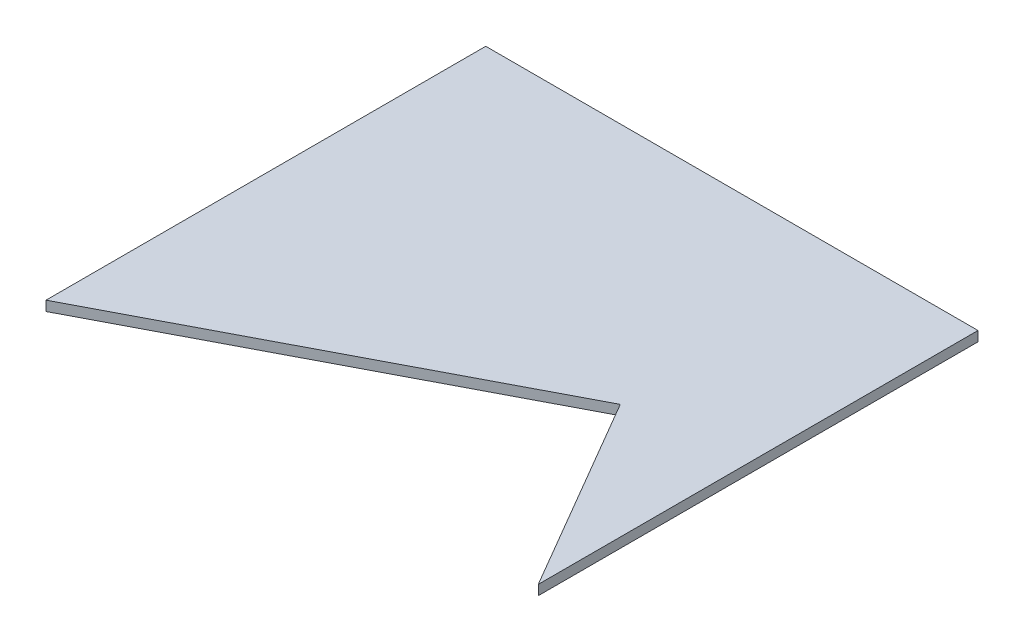
SolidWorks part; units mm, degrees
ref_plane "Front Plane" through (0, 0, 0) normal (0, 0, 1) x (1, 0, 0)
ref_plane "Top Plane" through (0, 0, 0) normal (0, 1, 0) x (1, 0, 0)
ref_plane "Right Plane" through (0, 0, 0) normal (1, 0, 0) x (0, 0, -1)
sketch "Sketch1" plane through (0, 0, 0) normal (0, 1, 0) x (1, 0, 0)
  line L0 (-75, -37) -> (-75, -97)
  line L1 (-75, -37) -> (75, -37)
  line L2 (-75, -37) -> (-75, 37)
  line L3 (-75, 37) -> (75, 37)
  line L4 (75, -37) -> (75, 37)
  line L5 (-75, -37) -> (75, 37) construction
  line L6 (-75, 37) -> (75, -37) construction
  line L7 (-75, -97) -> (40, -37)
  line L8 (40, -37) -> (75, -97)
  line L9 (75, -97) -> (75, -37)
  point P0 (0, 0)
  dimension "D1" = 150
  dimension "D2" = 74
  dimension "D3" = 35
  dimension "D4" = 60
extrude "Boss-Extrude1" add sketch "Sketch1" along normal blind 3 contours L0 L7 L1 | L1 L4 L3 L2 | L8 L9 L1 region at (-36.6667, 0, 57) region at (0, 0, 0) region at (63.3333, 0, 57)
